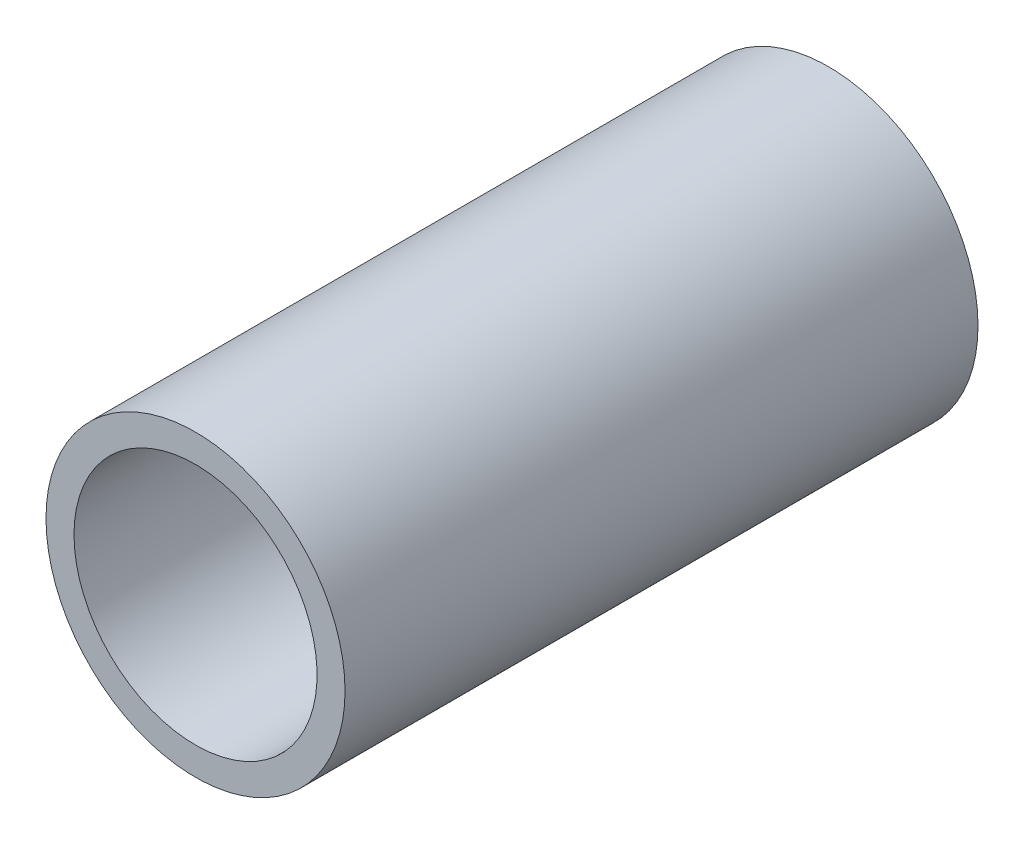
SolidWorks part; units mm, degrees
ref_plane "Front Plane" through (0, 0, 0) normal (0, 0, 1) x (1, 0, 0)
ref_plane "Top Plane" through (0, 0, 0) normal (0, 1, 0) x (1, 0, 0)
ref_plane "Right Plane" through (0, 0, 0) normal (1, 0, 0) x (0, 0, -1)
sketch "Sketch1" plane through (0, 0, 0) normal (0, 0, 1) x (1, 0, 0)
  circle A0 centre (0, 0) radius 1.5
  dimension "D1" = 3
extrude "Boss-Extrude1" add sketch "Sketch1" along normal blind 6.35
hole_wizard "#2 Clearance Hole2" positions "Sketch6" profile "Sketch5" hole size "#2" standard "ANSI Inch" end condition through all
sketch "Sketch6" plane through (0, 0, 0) normal (0, 0, -1) x (-1, 0, 0)
  point P0 (0, 0)
sketch "Sketch5" plane through (0, 0, 0) normal (1, 0, 0) x (0, 1, 0)
  line L0 (0, 0) -> (0, 6.35)
  line L1 (0, 6.35) -> (1.2192, 6.35)
  line L2 (1.2192, 6.35) -> (1.2192, 0)
  line L5 (1.2192, 0) -> (0, 0)
  line L11 (0, -6.35) -> (0, 107.95) construction
  dimension "Thru Hole Dia." = 2.4384
  dimension "Thru Hole Depth" = 6.35
